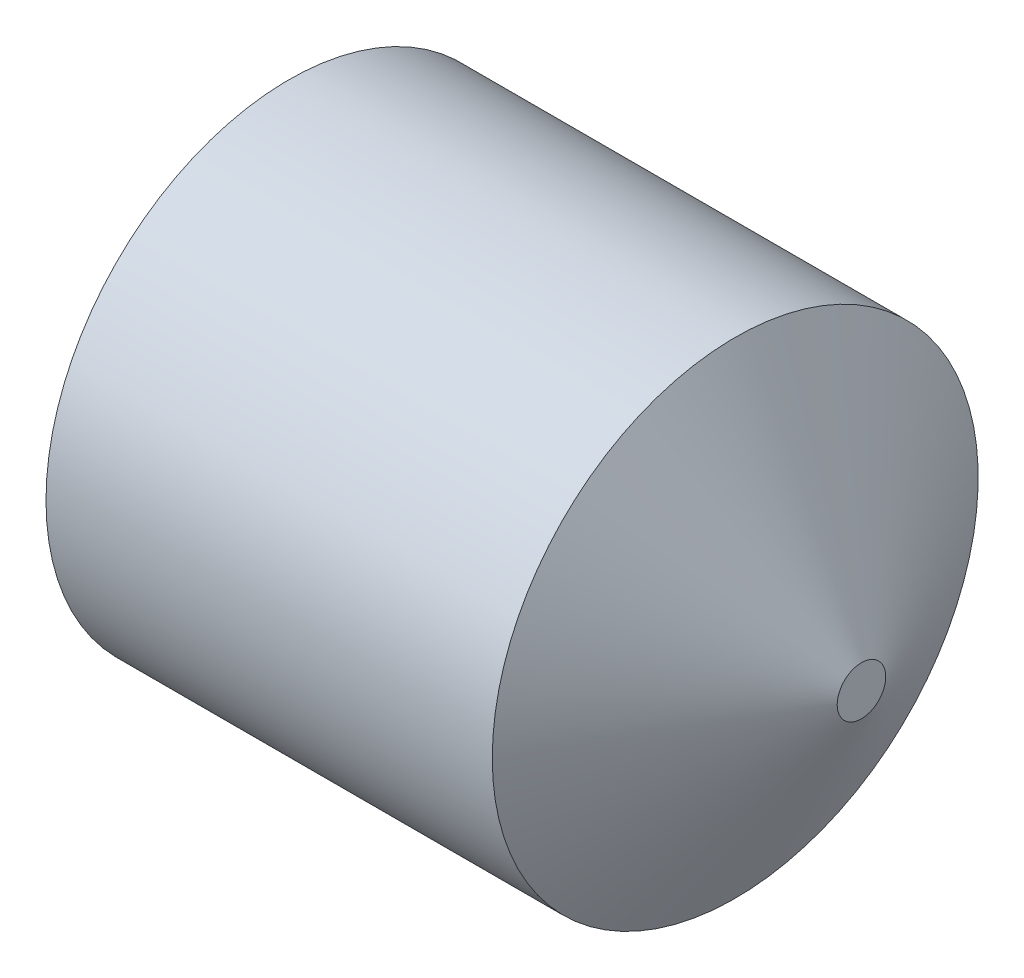
SolidWorks part; units mm, degrees
ref_plane "Front Plane" through (0, 0, 0) normal (0, 0, 1) x (1, 0, 0)
ref_plane "Top Plane" through (0, 0, 0) normal (0, 1, 0) x (1, 0, 0)
ref_plane "Right Plane" through (0, 0, 0) normal (1, 0, 0) x (0, 0, -1)
sketch "BodySke" plane through (0, 0, 0) normal (0, 0, 1) x (1, 0, 0)
  line L0 (0, 0) -> (3.28, 0) construction
  line L1 (2, 0) -> (2, 0.08)
  line L2 (2, 0.08) -> (1.5843, 0.8)
  line L3 (1.5843, 0.8) -> (0, 0.8)
  line L4 (0, 0.8) -> (0, 0)
  line L5 (0, 0) -> (2, 0)
  line L6 (1.65, 1.0236) -> (1.65, -0.6432) construction
  point P5 (0, 0.601)
  dimension "Minor_dia" = 1.202
  dimension "Angle" = 60
  dimension "Advance" = 0.35
revolve "BaseBody" add sketch "BodySke" angle 360 about L0
cosmetic thread "ThreadCosmetic" [suppressed] parameters "Minor_dia"=1.202
sketch "HeadChamferSke" plane through (0, 0, 0) normal (0, 0, 1) x (1, 0, 0)
  line L0 (0, 0) -> (2.4505, 0) construction
  line L1 (0, 0.8) -> (0, 0.601)
  line L2 (0, 0.8) -> (0.1149, 0.8)
  line L3 (0.1149, 0.8) -> (0, 0.601)
  line L4 (1.5843, 0.8) -> (0, 0.8) construction
  line L5 (0, 0.8) -> (0, -0.8) construction
  line L6 (0, 0.8) -> (0, 0) construction
  dimension "Angle" = 30
revolve "HeadChamfer" cut sketch "HeadChamferSke" angle 360 about L0
sketch "HexagonSocketSke" plane through (0, 0, 0) normal (-1, 0, 0) x (0, 0, 1)
  line L1 (0, 0.4041) -> (-0.35, 0.2021)
  line L2 (-0.35, 0.2021) -> (-0.35, -0.2021)
  line L3 (-0.35, -0.2021) -> (0, -0.4041)
  line L4 (0, -0.4041) -> (0.35, -0.2021)
  line L5 (0.35, -0.2021) -> (0.35, 0.2021)
  line L6 (0.35, 0.2021) -> (0, 0.4041)
  circle A0 centre (0, 0) radius 0.35 construction
  dimension "Hexagon_Width" = 0.7
extrude "HexagonSocket" cut sketch "HexagonSocketSke" against normal blind 0.7
sketch "ThdSchSke" plane through (0, 0, 0) normal (0, 0, 1) x (1, 0, 0)
  line L0 (0, 0) -> (2.6881, 0) construction
  line L1 (0.2351, 1.0298) -> (0.2351, 0.8)
  line L2 (0.2351, 1.0298) -> (0.4649, 1.0298)
  line L3 (0.4649, 1.0298) -> (0.4649, 0.8)
  line L4 (0.4649, 0.8) -> (0.35, 0.601)
  line L5 (0.35, 0.601) -> (0.2351, 0.8)
  line L6 (1.5843, 0.8) -> (0.1149, 0.8) construction
  dimension "D1" = 0.35
revolve "ThreadSchematic" [suppressed] cut sketch "ThdSchSke" angle 360 about L0
pattern_linear "ThdSchPat" [suppressed] count 4 along (1, 0, 0) of bodies 104
equation "\"Minor_dia@ThreadCosmetic\" = \"Minor_dia@BodySke\""
equation "\"D1@ThdSchSke\" = \"Advance@BodySke\""
equation "\"Advance@ThdSchPat\" = \"Advance@BodySke\""
equation "\"D1@ThdSchPat\" =  int(  ( \"Length@BodySke\" -  ( \"Diameter@BodySke\" / 2 - \"Chamfer_End@BodySke\" / 2 ) * 0.55  )  / \"Advance@BodySke\"  )  "
